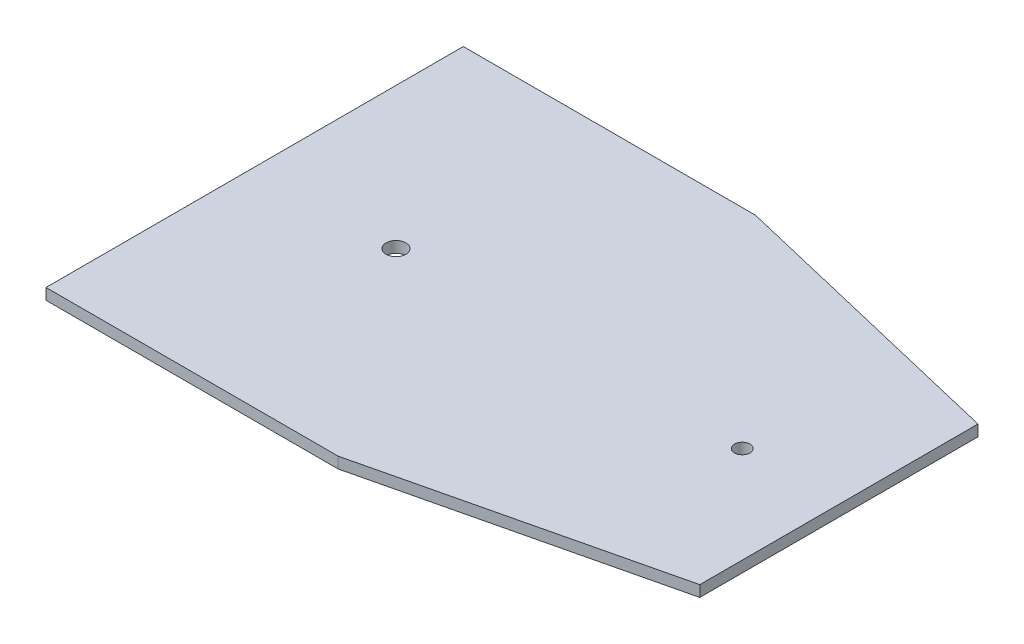
SolidWorks part; units mm, degrees
material "Carvalho"
ref_plane "Plano frontal" through (0, 0, 0) normal (0, 0, 1) x (1, 0, 0)
ref_plane "Plano superior" through (0, 0, 0) normal (0, 1, 0) x (1, 0, 0)
ref_plane "Plano direito" through (0, 0, 0) normal (1, 0, 0) x (0, 0, -1)
sketch "Esboço1" plane through (0, 0, 0) normal (0, 1, 0) x (1, 0, 0)
  line L0 (210, 50) -> (105, 75)
  line L1 (0, -75) -> (105, -75)
  line L2 (0, -75) -> (0, 75)
  line L3 (0, 75) -> (105, 75)
  line L4 (210, -50) -> (210, 50)
  line L7 (105, -75) -> (210, -50)
  line L8 (-14.8259, 0) -> (14.392, 0) construction
  line L9 (0, 21.2472) -> (0, -16.7598) construction
  circle A0 centre (50.8, 0) radius 3.5719
  circle A1 centre (175.26, 0) radius 2.7781
  point P0 (0, 0)
  dimension "D3" = 7.1437
  dimension "D5" = 5.5562
  dimension "D1" = 25
  dimension "D2" = 150
  dimension "D4" = 50.8
  dimension "D6" = 210
  dimension "D7" = 175.26
  dimension "D8" = 105
extrude "Ressalto-extrusão1" add sketch "Esboço1" along normal blind 4
